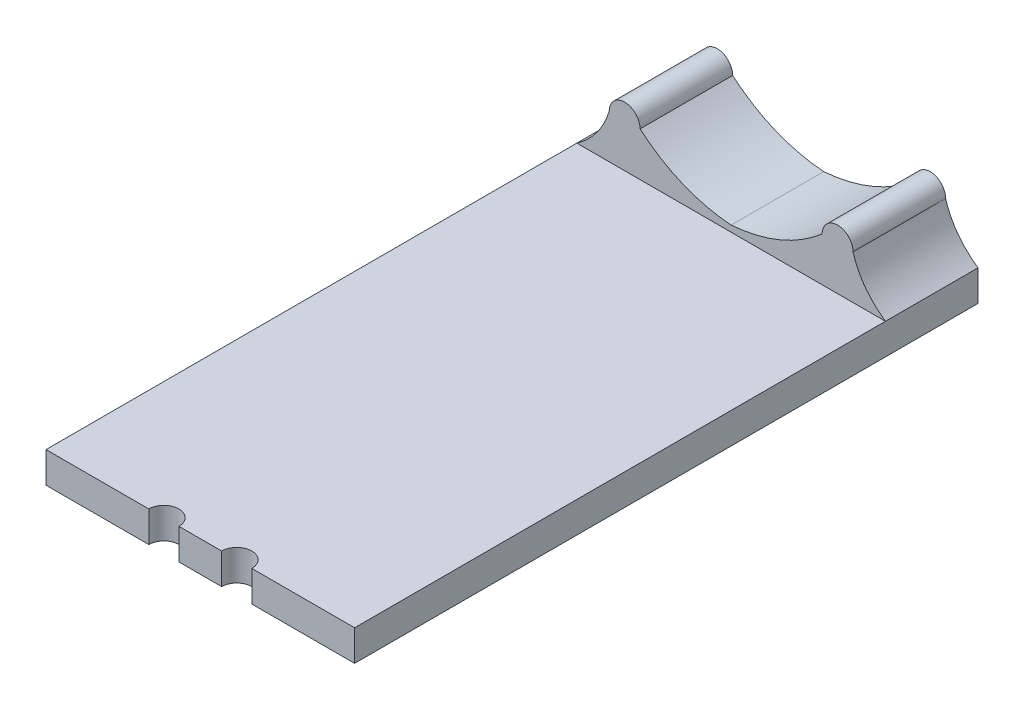
SolidWorks part; units mm, degrees
ref_plane "Front Plane" through (0, 0, 0) normal (0, 0, 1) x (1, 0, 0)
ref_plane "Top Plane" through (0, 0, 0) normal (0, 1, 0) x (1, 0, 0)
ref_plane "Right Plane" through (0, 0, 0) normal (1, 0, 0) x (0, 0, -1)
sketch "Sketch1" plane through (0, 0, 0) normal (0, 0, 1) x (1, 0, 0)
  line L0 (-996.8903, -40.64) -> (49003.1097, -40.64) construction
  line L1 (0, -1000) -> (0, 49000) construction
  line L2 (0, 0) -> (-23.4635, -40.64) construction
  line L3 (0, 0) -> (-40.64, -40.64) construction
  line L4 (-31.75, -46.99) -> (-31.75, -53.34)
  line L5 (-31.75, -53.34) -> (31.75, -53.34)
  line L6 (31.75, -46.99) -> (31.75, -53.34)
  circle A0 centre (0, 0) radius 40.64 construction
  arc A1 (-18.7325, -37.9449) -> (-25.0825, -37.9449) centre (-21.9075, -37.9449) ccw
  arc A2 (18.7325, -37.9449) -> (25.0825, -37.9449) centre (21.9075, -37.9449) cw
  spline S0 degree 2 poles (-18.7325, -37.9449) (-10.6333, -44.8669) (0, -45.72) knots 0 0 0 1 1 1
  spline S1 degree 2 poles (-25.0825, -37.9449) (-26.7486, -43.4895) (-31.75, -46.99) knots 0 0 0 1 1 1
  spline S2 degree 2 poles (25.0825, -37.9449) (26.7486, -43.4895) (31.75, -46.99) knots 0 0 0 1 1 1
  spline S3 degree 2 poles (18.7325, -37.9449) (10.6333, -44.8669) (0, -45.72) knots 0 0 0 1 1 1
  point P13 (0, -53.34)
  point P25 (-31.75, -46.7758)
  dimension "D1" = 81.28
  dimension "D3" = 6.35
  dimension "D5" = 5.08
  dimension "D2" = 30
  dimension "D4" = 45
  dimension "D6" = 31.75
  dimension "D7" = 6.35
  dimension "D8" = 6.35
extrude "Boss-Extrude1" add sketch "Sketch1" along normal mid plane 19.05
sketch "Sketch4" plane through (0, 0, 9.525) normal (0, 0, 1) x (1, 0, 0)
  line L1 (-31.75, -46.99) -> (31.75, -46.99)
  line L2 (-31.75, -46.99) -> (-31.75, -53.34)
  line L3 (-31.75, -53.34) -> (31.75, -53.34)
  line L4 (31.75, -46.99) -> (31.75, -53.34)
extrude "Boss-Extrude2" add sketch "Sketch4" along normal blind 109.22
sketch "Sketch5" plane through (0, -46.99, 0) normal (0, 1, 0) x (1, 0, 0)
  line L0 (31.75, -118.745) -> (-31.75, -118.745) construction
  line L1 (0, -1000) -> (0, 49000) construction
  circle A0 centre (7.5, -118.745) radius 3.1
  circle A1 centre (-7.5, -118.745) radius 3.1
  dimension "D1" = 6.2
  dimension "D2" = 7.5
extrude "Cut-Extrude1" cut sketch "Sketch5" against normal through all
